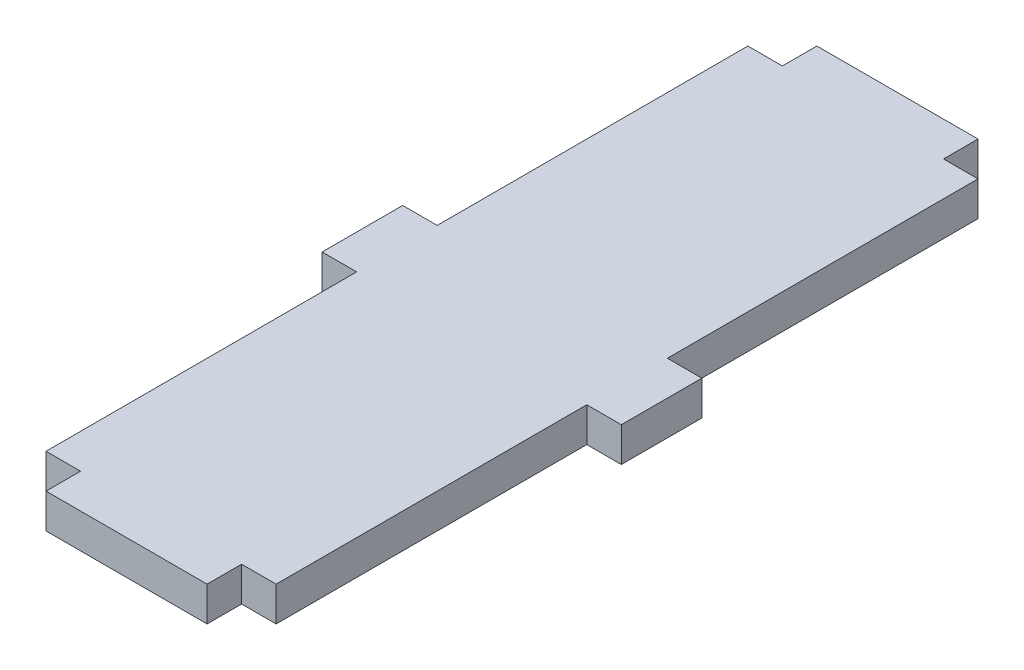
SolidWorks part; units mm, degrees
ref_plane "Alzado" through (0, 0, 0) normal (0, 0, 1) x (1, 0, 0)
ref_plane "Planta" through (0, 0, 0) normal (0, 1, 0) x (1, 0, 0)
ref_plane "Vista lateral" through (0, 0, 0) normal (1, 0, 0) x (0, 0, -1)
sketch "Croquis2" plane through (0, 0, 0) normal (0, 1, 0) x (1, 0, 0)
  line L1 (-4.5, 22) -> (-4.5, 15)
  line L2 (15.5, -15) -> (15.5, -12)
  line L3 (15.5, 49) -> (15.5, 52)
  line L4 (15.5, 52) -> (1.5, 52)
  line L5 (18.5, -12) -> (15.5, -12)
  line L6 (1.5, 52) -> (1.5, 49)
  line L7 (15.5, 52) -> (15.5, 49)
  line L8 (-1.5, 49) -> (1.5, 49)
  line L9 (18.5, 49) -> (18.5, 22)
  line L10 (-1.5, 15) -> (-4.5, 15)
  line L11 (-1.5, -12) -> (-1.5, 15)
  line L12 (15.5, -12) -> (15.5, -15)
  line L13 (1.5, 49) -> (1.5, 52)
  line L14 (-1.5, 49) -> (-1.5, 22)
  line L15 (-1.5, 22) -> (-4.5, 22)
  line L16 (15.5, 49) -> (18.5, 49)
  line L17 (1.5, -12) -> (1.5, -15)
  line L18 (18.5, -12) -> (18.5, 15)
  line L19 (18.5, 15) -> (21.5, 15)
  line L20 (-1.5, -12) -> (1.5, -12)
  line L21 (21.5, 22) -> (21.5, 15)
  line L22 (1.5, -15) -> (1.5, -12)
  line L23 (15.5, -15) -> (1.5, -15)
  line L24 (18.5, 22) -> (21.5, 22)
  dimension "D1" = 7
  dimension "D2" = 27
  dimension "D3" = 14
  dimension "D4" = 3
  dimension "D5" = 27
  dimension "D6" = 7
  dimension "D7" = 27
  dimension "D9" = 27
  dimension "D10" = 3
  dimension "D11" = 3
  dimension "D13" = 3
extrude "Saliente-Extruir1" add sketch "Croquis2" along normal blind 3 contours L23 L9 L8 L10 L11 L20 L17 region at (8.5, 0, -18.5)
